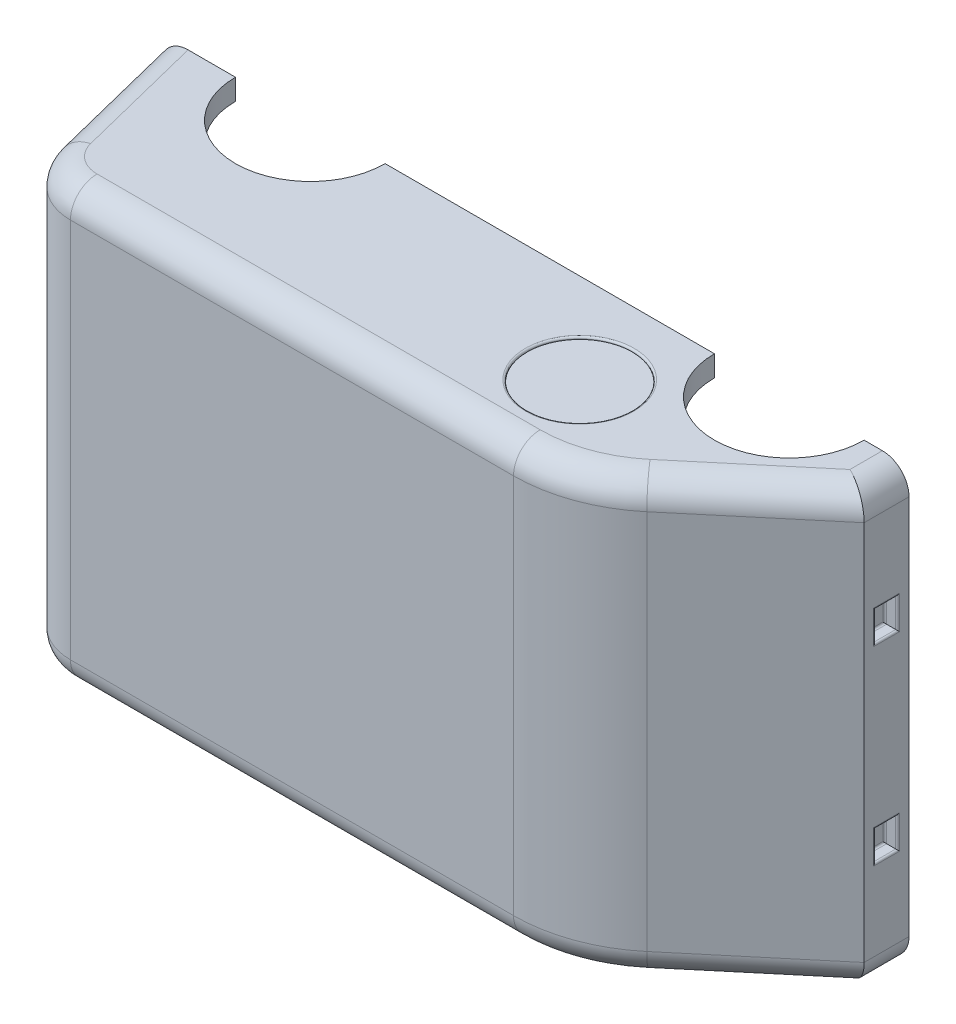
SolidWorks part; units mm, degrees
ref_plane "Front Plane" through (0, 0, 0) normal (0, 0, 1) x (1, 0, 0)
ref_plane "Top Plane" through (0, 0, 0) normal (0, 1, 0) x (1, 0, 0)
ref_plane "Right Plane" through (0, 0, 0) normal (1, 0, 0) x (0, 0, -1)
sketch "Sketch1" plane through (0, 0, 0) normal (0, 0, 1) x (1, 0, 0)
  line L1 (0, 0) -> (250, 0)
  line L2 (0, 0) -> (0, 145)
  line L3 (0, 145) -> (250, 145)
  line L4 (250, 0) -> (250, 145)
  dimension "D1" = 250
  dimension "D2" = 145
extrude "Boss-Extrude1" add sketch "Sketch1" along normal blind 60 contours L2 L1 L4 L3
sketch "Sketch2" plane through (0, 0, 0) normal (0, -1, 0) x (1, 0, 0)
  line L0 (125, 60) -> (125, 0)
  line L1 (0, 60) -> (250, 60) construction
  line L2 (0, 0) -> (250, 0) construction
  line L3 (196.3711, 60) -> (250, 15)
  line L4 (250, 60) -> (250, 0) construction
  line L5 (250, 15) -> (250, 60)
  line L6 (250, 60) -> (196.3711, 60)
  line L7 (15, 60) -> (0, 0)
  line L8 (0, 0) -> (0, 60)
  line L9 (0, 60) -> (15, 60)
  line M8 (250, 0) -> (250, 60)
  line M9 (250, 60) -> (0, 60)
  dimension "D1" = 50
  dimension "D2" = 15
  dimension "D3" = 15
extrude "Cut-Extrude1" cut sketch "Sketch2" against normal through all contours L3 M9 M8 | L9 L7 L8 region at (232.1237, 0, 45)
sketch "Sketch8" plane through (0, 0, 0) normal (0, -1, 0) x (1, 0, 0)
  line L0 (0, 0) -> (250, 0) construction
  line L2 (250, 15) -> (250, 0) construction
  circle A0 centre (210, 0) radius 25
  circle A1 centre (50, 0) radius 25
  line M6 (0, 0) -> (250, 0)
  dimension "D1" = 50
  dimension "D2" = 40
  dimension "D3" = 50
ref_plane "Plane2" through (0, 72.5, 0) normal (0, 1, 0) x (1, 0, 0)
sketch "Sketch7" plane through (0, 72.5, 0) normal (0, 1, 0) x (1, 0, 0)
  line L3 (250, -15) -> (250, 0) construction
  line L4 (240, 1.2127) -> (240, -16.864)
  line L9 (240, 1.2127) -> (4.8507, 1.2127)
  line L13 (245, -12.6685) -> (194.5512, -55)
  line L14 (245, 0) -> (245, -12.6685)
  line L15 (194.5512, -55) -> (18.9039, -55)
  line L16 (18.9039, -55) -> (4.8507, 1.2127)
  line L17 (240, -16.864) -> (194.5512, -55)
  line L19 (194.5512, -55) -> (18.9039, -55)
  line L20 (18.9039, -55) -> (4.8507, 1.2127)
  dimension "D2" = 10
  dimension "D1" = 5
extrude "Cut-Extrude2" cut sketch "Sketch7" against normal offset from surface 7 and the other way offset from surface 7 up to face at (142.2742, 0, 27) other way up to face at (142.2742, 145, 27)
extrude "Cut-Extrude3" cut sketch "Sketch8" against normal blind 185 contours A1 M6 | A0 M6 region at (210, 0, 10.6103) region at (50, 0, 10.6103)
ref_plane "Plane3" through (0, 36.25, 0) normal (0, 1, 0) x (1, 0, 0)
ref_plane "Plane4" through (0, 108.75, 0) normal (0, 1, 0) x (1, 0, 0)
ref_plane "Plane5" through (170, 0, 0) normal (1, 0, 0) x (0, 0, -1)
ref_plane "Plane6" through (0, 0, 30) normal (0, 0, 1) x (1, 0, 0)
sketch "Sketch9" plane through (0, 0, 0) normal (0, 0, -1) x (-1, 0, 0)
  line L2 (-235, 0) -> (-233.3632, -0.3016)
  line L3 (-233.3632, -0.3016) -> (-233.3632, -8.7965)
  line L4 (-233.3632, -8.7965) -> (-264.6405, -8.7965)
  line L5 (-264.6405, -8.7965) -> (-264.6405, 5.015)
  line L6 (-257.1617, 15.3583) -> (-264.6405, 5.015)
  line L7 (-269.197, 13.9998) -> (-250, 14) construction
  line L9 (-250, 0) -> (-250, 145) construction
  arc A1 (-250, 14) -> (-235, 0) centre (-231.5477, 18.7346) ccw
  arc A2 (-250, 14) -> (-257.1617, 15.3583) centre (-253.8994, 12.9995) ccw
  point P1 (-257.4452, 11.5115)
  point P4 (-244.5459, 4.808)
  point P6 (-250, 14.3729)
  dimension "D2" = 19.05
ref_plane "Plane7" through (0, 4.808, 0) normal (0, -1, 0) x (-1, 0, 0)
sketch "Sketch12" plane through (0, 4.808, 0) normal (0, -1, 0) x (-1, 0, 0)
  line L4 (-196.3711, -60) -> (-250, -15) construction
  line L5 (-231.0899, -30.8675) -> (-184.34, -69.9976)
  arc A1 (-244.5459, 0) -> (-231.0899, -30.8675) centre (-206.8851, -1.9493) ccw
fillet "Fillet1" radius 8.89 8 edges at (223.1855, 0, 37.5) (250, 0, 7.5) (7.5, 0, 30) (105.6855, 0, 60) (7.5, 145, 30) (105.6855, 145, 60) (223.1855, 145, 37.5) (250, 145, 7.5) tangent propagation no
fillet "Fillet2" radius 50.8 3 edges at (195.4234, 2.6038, 57.3962) (195.4234, 142.3962, 57.3962) (196.3711, 72.5, 60)
fillet "Fillet3" radius 19.05 3 edges at (17.033, 2.6038, 57.3962) (17.033, 142.3962, 57.3962) (15, 72.5, 60)
sketch "Sketch13" plane through (250, 0, 0) normal (1, 0, 0) x (0, 0, -1)
  line L24 (-3.8, 45.7) -> (-11.2, 45.7)
  line L25 (-11.2, 45.7) -> (-11.2, 35.8)
  line L26 (-3.8, 35.8) -> (-3.8, 45.7)
  line L27 (-11.2, 35.8) -> (-3.8, 35.8)
  line L28 (-3.8, 45.7) -> (-11.2, 45.7)
  line L29 (-11.2, 45.7) -> (-11.2, 35.8)
  line L30 (-3.8, 35.8) -> (-3.8, 45.7)
  line L31 (-11.2, 35.8) -> (-3.8, 35.8)
  dimension "D1" = 0.05
extrude "Cut-Extrude4" cut sketch "Sketch13" against normal blind 4.318
fillet "Fillet4" radius 0.635 8 edges at (245.682, 35.8, 7.5) (245.682, 40.75, 11.2) (245.682, 45.7, 7.5) (245.682, 40.75, 3.8) (250, 35.8, 7.5) (250, 40.75, 11.2) (250, 45.7, 7.5) (250, 40.75, 3.8)
mirror "Mirror2" about plane through (0, 72.5, 0) normal (0, 1, 0) of "Cut-Extrude4", "Fillet4"
sketch "Sketch14" plane through (0, 0, 0) normal (0, -1, 0) x (1, 0, 0)
  circle A3 centre (170, 30) radius 17.5254
  circle A4 centre (170, 30) radius 17.5254
  point P2 (169.8559, 30)
  dimension "D1" = 0.0254
extrude "Cut-Extrude5" cut sketch "Sketch14" against normal blind 0.75 contours A4
fillet "Fillet5" radius 0.635 1 edges at (170, 0, 12.4746)
mirror "Mirror4" about plane through (0, 72.5, 0) normal (0, 1, 0) of "Cut-Extrude5"
fillet "Fillet6" radius 0.635 1 edges at (170, 145, 12.4746)
sketch "Sketch16" plane through (0, 0, 0) normal (-0.9701, 0, 0.2425) x (0.2425, 0, 0.9701)
  line L20 (35.1285, 103.7) -> (35.1285, 113.8)
  line L21 (20.0285, 103.7) -> (35.1285, 103.7)
  line L22 (20.0285, 113.8) -> (20.0285, 103.7)
  line L23 (35.1285, 113.8) -> (20.0285, 113.8)
  line L24 (35.1285, 103.7) -> (35.1285, 113.8)
  line L25 (20.0285, 103.7) -> (35.1285, 103.7)
  line L26 (20.0285, 113.8) -> (20.0285, 103.7)
  line L27 (35.1285, 113.8) -> (20.0285, 113.8)
  dimension "D1" = 0.05
extrude "Cut-Extrude6" cut sketch "Sketch16" against normal blind 3.05 contours L24 L27 L26 L25
mirror "Mirror5" about plane through (0, 72.5, 0) normal (0, 1, 0) of "Cut-Extrude6"
ref_plane "Plane8" through (0, 0, 0) normal (-0.9701, 0, 0.2425) x (0.2425, 0, 0.9701)
ref_plane "Plane9" through (6.6888, 0, 26.7551) normal (0.2425, 0, 0.9701) x (0.9701, 0, -0.2425)
equation "\"tol\"= 0.05mm"
equation "\"D1@Sketch16\"=\"tol\""
equation "\"D1@Cut-Extrude6\"=3mm+\"tol\""
equation "\"D1@Sketch13\"=\"tol\""
